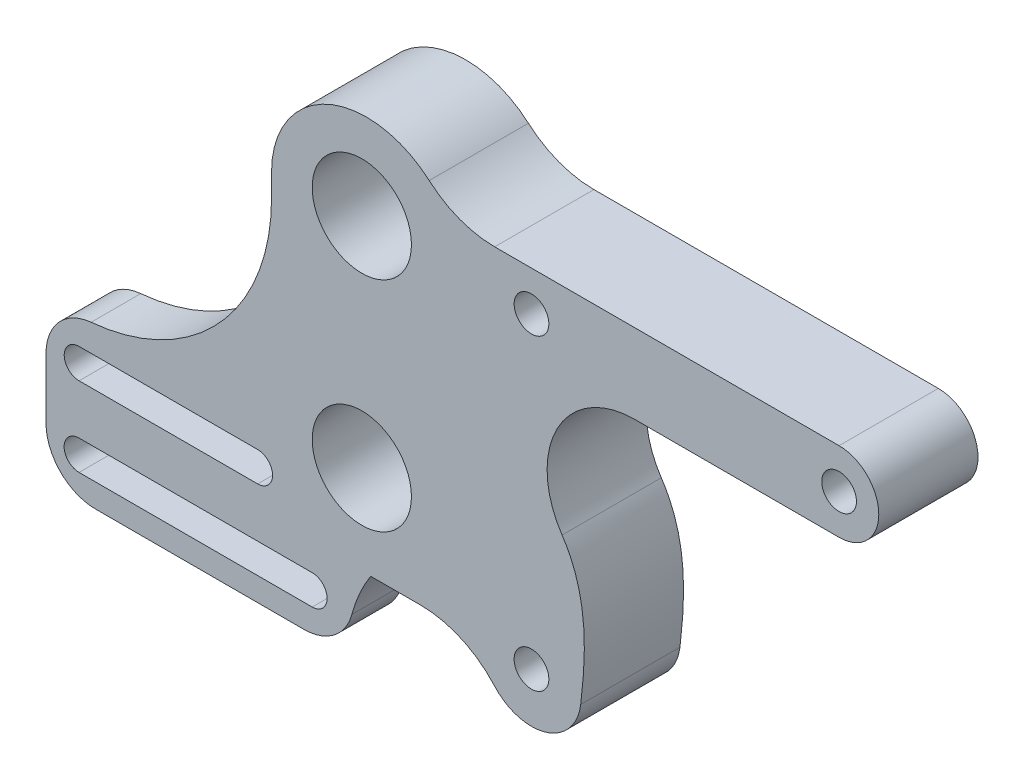
SolidWorks part; units mm, degrees
material "ABS generico"
ref_plane "Piano frontale" through (0, 0, 0) normal (0, 0, 1) x (1, 0, 0)
ref_plane "Piano superiore" through (0, 0, 0) normal (0, 1, 0) x (1, 0, 0)
ref_plane "Piano destro" through (0, 0, 0) normal (1, 0, 0) x (0, 0, -1)
sketch "Sketch1" plane through (0, 0, 0) normal (0, 0, 1) x (1, 0, 0)
  line L0 (59.1153, 43.5513) -> (93.8228, 43.5513)
  line L2 (36.6269, 38.8486) -> (36.6269, 18.5513)
  line L3 (51.6425, 8.5513) -> (46.6269, 8.5513)
  line L4 (93.8228, 35.5513) -> (73.2211, 35.5513)
  line L6 (62.8228, -5.7466) -> (62.8228, 55.7339) construction
  line L7 (10.2847, 39.5513) -> (106.4029, 39.5513) construction
  arc A0 (59.096, 5.2179) -> (65.7153, 4.4728) centre (62.8228, 8.5513) ccw
  arc A1 (93.8228, 35.5513) -> (93.8228, 43.5513) centre (93.8228, 39.5513) ccw
  arc A2 (52.5151, 46.0388) -> (36.6269, 38.8486) centre (46.198, 38.8486) ccw
  arc A3 (46.6269, 8.5513) -> (36.6269, 18.5513) centre (46.6269, 18.5513) cw
  arc A4 (73.2211, 35.5513) -> (65.9057, 21.7942) centre (73.2211, 26.7278) ccw
  circle A5 centre (93.8228, 39.5513) radius 1.75
  circle A6 centre (62.8228, 39.5513) radius 1.75
  circle A7 centre (62.8228, 8.5513) radius 1.75
  arc A10 (65.7153, 4.4728) -> (67.786, 7.9453) centre (62.8228, 8.5513) ccw
  arc A11 (59.096, 5.2179) -> (51.6425, 8.5513) centre (51.6425, -1.4487) ccw
  arc A12 (59.1153, 43.5513) -> (52.5151, 46.0388) centre (59.1153, 53.5513) cw
  circle A13 centre (45.7251, 39.5513) radius 5
  circle A14 centre (45.7251, 17.5513) radius 5
  spline S0 degree 3 poles (65.9057, 21.7942) (68.5106, 17.9318) (68.3976, 12.9554) (67.786, 7.9453) knots 0 0 0 0 1 1 1 1
  point P21 (45.7251, 39.5513)
  point P22 (45.7251, 17.5513)
  point P41 (57.8228, 8.5513)
  dimension "D2" = 31
  dimension "D4" = 10
  dimension "D6" = 10
  dimension "D7" = 8
  dimension "D9" = 5
  dimension "D10" = 10
  dimension "D11" = 10
  dimension "D12" = 10
  dimension "D13" = 3.5
  dimension "D1" = 22
  dimension "D3" = 31
extrude "Boss-Extrude1" add sketch "Sketch1" against normal blind 10
sketch "Sketch2" plane through (0, 0, 0) normal (0, 0, 1) x (1, 0, 0)
  line L0 (45.6366, 8.5513) -> (43.8969, 0.5513)
  line L1 (39.149, 16.5513) -> (41.0064, 12.5513)
  line L2 (39.149, 16.5513) -> (13.8969, 16.5513)
  line L3 (45.6366, 10.8576) -> (45.6366, 8.5513)
  line L5 (43.8969, 0.5513) -> (13.8969, 0.5513)
  line L9 (13.8969, 16.5513) -> (13.8969, 0.5513)
  line L14 (41.0064, 12.5513) -> (45.6366, 10.8576)
  point P0 (49.8144, 8.5513)
  point P1 (-4.8939, 8.5513)
  point P4 (49.8144, 16.5513)
  point P5 (-4.8939, 16.5513)
  point P11 (45.6366, 16.5513)
  point P12 (45.6366, 5.6789)
  point P14 (-4.3634, 5.6789)
  dimension "D1" = 30
extrude "Extrude1" add sketch "Sketch2" against normal blind 5
fillet "Fillet2" radius 20 1 edges at (36.829, 16.5513, -2.5)
fillet "Fillet3" radius 5 1 edges at (13.8969, 16.5513, -2.5)
fillet "Fillet5" radius 5 1 edges at (13.8969, 0.5513, -2.5)
sketch "Sketch3" plane through (0, 0, -5) normal (0, 0, -1) x (-1, 0, 0)
  line L0 (-37.1999, 8.4181) -> (8.3883, 8.4181) construction
  line L1 (-40.7251, 17.5513) -> (-40.7251, -8.1457) construction
  line L2 (-37.1999, 4.4181) -> (8.3883, 4.4181) construction
  line L3 (-37.1999, 12.4181) -> (8.3883, 12.4181) construction
  line L4 (-17.2308, 12.4181) -> (-35.2308, 12.4181) construction
  line L5 (-17.2308, 10.9181) -> (-35.2308, 10.9181)
  line L6 (-17.2308, 13.9181) -> (-35.2308, 13.9181)
  line L7 (-17.2251, 4.4181) -> (-40.7251, 4.4181) construction
  line L8 (-17.2251, 2.9181) -> (-40.7251, 2.9181)
  line L9 (-17.2251, 5.9181) -> (-40.7251, 5.9181)
  arc A0 (-17.2308, 10.9181) -> (-17.2308, 13.9181) centre (-17.2308, 12.4181) ccw
  arc A1 (-35.2308, 13.9181) -> (-35.2308, 10.9181) centre (-35.2308, 12.4181) ccw
  arc A2 (-17.2251, 2.9181) -> (-17.2251, 5.9181) centre (-17.2251, 4.4181) ccw
  arc A3 (-40.7251, 5.9181) -> (-40.7251, 2.9181) centre (-40.7251, 4.4181) ccw
  circle A4 centre (-45.7251, 17.5513) radius 5 construction
  point P8 (-26.2308, 12.4181)
  point P14 (-28.9751, 4.4181)
  dimension "D1" = 18
  dimension "D2" = 23.5
extrude "Extrude2" cut sketch "Sketch3" against normal blind 5
fillet "Fillet7" radius 475 1 edges at (45.6366, 8.6004, -2.5)
fillet "Fillet8" radius 15 1 edges at (45.6366, 8.5513, -2.5)
fillet "Fillet9" radius 5 1 edges at (43.8969, 0.5513, -2.5)
sketch "Sketch4" plane through (0, 0, -10) normal (0, 0, -1) x (-1, 0, 0)
  circle A0 centre (-62.8228, 39.5513) radius 3.5
  circle A1 centre (-93.8228, 39.5513) radius 3.5
  circle A2 centre (-62.8228, 8.5513) radius 3.5
  dimension "D1" = 7
  dimension "D2" = 2
  dimension "D3" = 2
extrude "Extrude3" cut sketch "Sketch4" against normal blind 1
